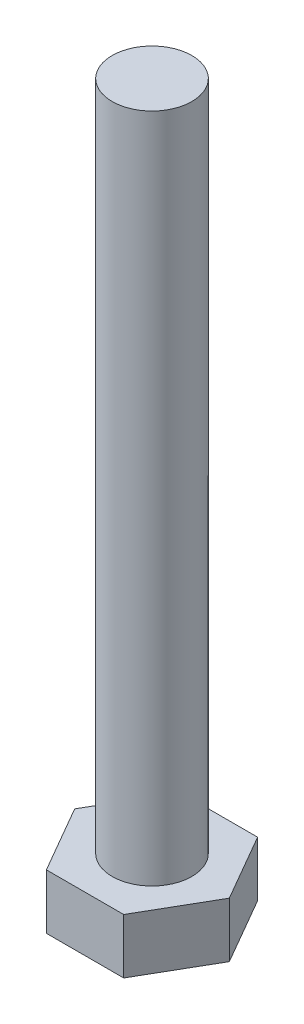
SolidWorks part; units mm, degrees
ref_plane "Front Plane" through (0, 0, 0) normal (0, 0, 1) x (1, 0, 0)
ref_plane "Top Plane" through (0, 0, 0) normal (0, 1, 0) x (1, 0, 0)
ref_plane "Right Plane" through (0, 0, 0) normal (1, 0, 0) x (0, 0, -1)
sketch "Sketch1" plane through (0, 0, 0) normal (0, 1, 0) x (1, 0, 0)
  line L1 (4.8497, -8.4) -> (9.6995, 0)
  line L2 (9.6995, 0) -> (4.8497, 8.4)
  line L3 (4.8497, 8.4) -> (-4.8497, 8.4)
  line L4 (-4.8497, 8.4) -> (-9.6995, 0)
  line L5 (-9.6995, 0) -> (-4.8497, -8.4)
  line L6 (-4.8497, -8.4) -> (4.8497, -8.4)
  circle A0 centre (0, 0) radius 8.4 construction
  circle A1 centre (0, 0) radius 5
  dimension "D2" = 10
  dimension "D1" = 16.8
extrude "Boss-Extrude1" add sketch "Sketch1" along normal blind 6.9
extrude "Boss-Extrude2" add sketch "Sketch1<2>" along normal blind 91.1 contours A1 region at (0, 0, 0)
sketch "Sketch1<2>" plane through (0, 0, 0) normal (0, 1, 0) x (1, 0, 0) same geometry as "Sketch1"
